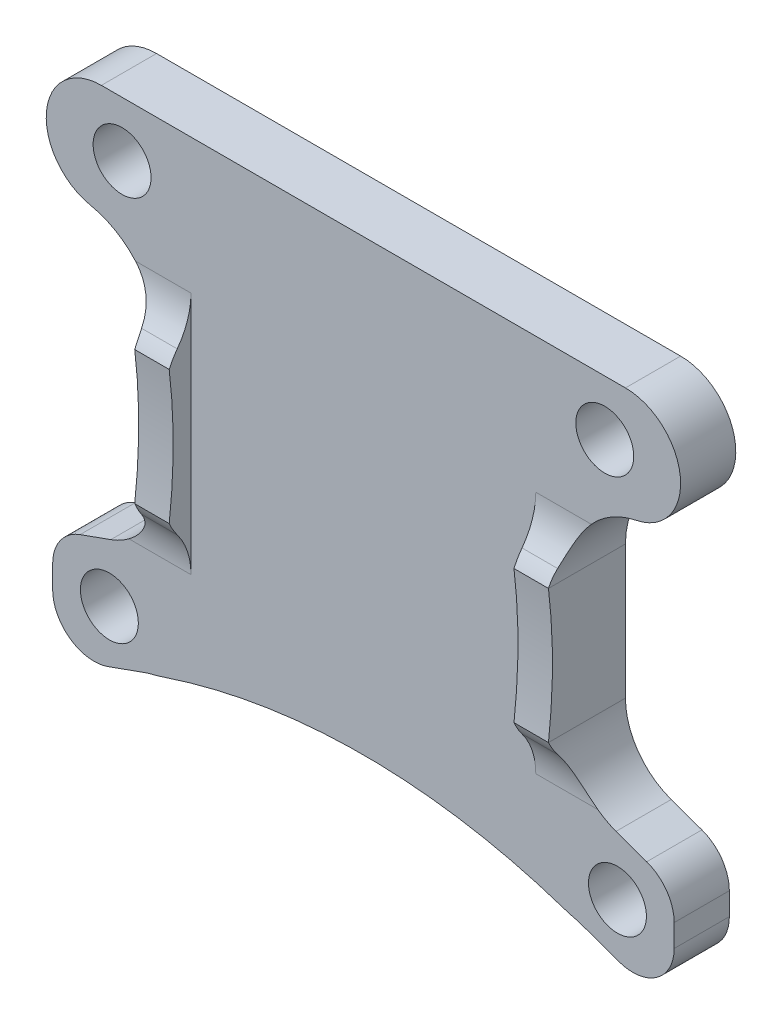
SolidWorks part; units mm, degrees
material "7075-T6 (SN)"
ref_plane "Ön Düzlem" through (0, 0, 0) normal (0, 0, 1) x (1, 0, 0)
ref_plane "Üst Düzlem" through (0, 0, 0) normal (0, 1, 0) x (1, 0, 0)
ref_plane "Sağ Düzlem" through (0, 0, 0) normal (1, 0, 0) x (0, 0, -1)
sketch "Çizim1" plane through (0, 0, 0) normal (0, 0, 1) x (1, 0, 0)
  line L1 (-14.1333, -17.5) -> (14.1333, -17.5)
  line L2 (-15, -5.9774) -> (-15, 9.5)
  line L3 (-15, 17.5) -> (15, 17.5)
  line L4 (15, -5.9774) -> (15, 9.5)
  line L5 (-15, -17.5) -> (15, 17.5) construction
  line L6 (-15, 17.5) -> (15, -17.5) construction
  line L7 (-15.8162, -17.7917) -> (-18.5235, -18.7594)
  line L8 (-18.3171, -10.6856) -> (-20.543, -11.4812)
  line L9 (-22.5333, -15.9344) -> (-22.5333, -14.3062)
  line L10 (0, -55) -> (0, 55) construction
  line L11 (15.8162, -17.7917) -> (18.5235, -18.7594)
  line L12 (22.5333, -15.9344) -> (22.5333, -14.3062)
  line L13 (18.3171, -10.6856) -> (20.543, -11.4812)
  line L14 (15, 9.5) -> (23, 9.5)
  line L15 (-15, 17.5) -> (-23, 17.5)
  line L17 (-15, 9.5) -> (-23, 9.5)
  line L18 (-23, 17.5) -> (-23, 9.5)
  line L19 (23, 17.5) -> (23, 9.5)
  line L20 (15, 17.5) -> (23, 17.5)
  arc A0 (-15, -5.9774) -> (-18.3171, -10.6856) centre (-20, -5.9774) cw
  arc A1 (-14.1333, -17.5) -> (-15.8162, -17.7917) centre (-14.1333, -22.5) ccw
  arc A2 (-18.5235, -18.7594) -> (-22.5333, -15.9344) centre (-19.5333, -15.9344) cw
  arc A3 (-20.543, -11.4812) -> (-22.5333, -14.3062) centre (-19.5333, -14.3062) ccw
  arc A4 (14.1333, -17.5) -> (15.8162, -17.7917) centre (14.1333, -22.5) cw
  arc A5 (18.5235, -18.7594) -> (22.5333, -15.9344) centre (19.5333, -15.9344) ccw
  arc A6 (15, -5.9774) -> (18.3171, -10.6856) centre (20, -5.9774) ccw
  arc A7 (20.543, -11.4812) -> (22.5333, -14.3062) centre (19.5333, -14.3062) cw
  point P0 (0, 0)
  point P11 (-15, -9.5)
  point P17 (-22.5333, -20.1926)
  point P20 (-22.5333, -12.1926)
  dimension "D5" = 5
  dimension "D6" = 5
  dimension "D7" = 3
  dimension "D1" = 30
  dimension "D2" = 35
  dimension "D3" = 8
  dimension "D4" = 8
  dimension "D8" = 8
  dimension "D9" = 8
extrude "Yükseklik-Ekstrüzyon1" add sketch "Çizim1" along normal blind 4
fillet "Radyus1" 2 edges at (23, 9.5, 2) (23, 17.5, 2) type full round first side face at (19, 9.5, 2) second side face at (0, 17.5, 2) middle face at (23, 13.5, 2)
fillet "Radyus2" 2 edges at (-23, 9.5, 2) (-23, 17.5, 2) type full round first side face at (-19, 9.5, 2) second side face at (-2, 17.5, 2) middle face at (-23, 13.5, 2)
sketch "Çizim2" plane through (0, 0, 0) normal (0, 0, -1) x (-1, 0, 0)
  circle A0 centre (0, 0) radius 9.5 construction
  point P3 (0, 9.5)
  point P7 (9.5, 0)
  point P8 (0, -9.5)
  point P9 (-9.5, 0)
  point P10 (0, 0)
  dimension "D1" = 19
sketch "Çizim5" plane through (0, 0, 0) normal (0, 0, -1) x (-1, 0, 0)
  line L0 (0, 55) -> (0, -55) construction
  circle A1 centre (-18.8837, -14.9121) radius 2 construction
  circle A2 centre (18.8837, -14.9121) radius 2 construction
  dimension "D1" = 4
fillet "Radyus3" radius 6 2 edges at (-15, 9.5, 2) (15, 9.5, 2)
sketch "Çizim8" plane through (15, 0, 0) normal (1, 0, 0) x (0, 0, -1)
  line L0 (-4, 3.702) -> (-4, -5.9774)
  line L1 (-4, 3.702) -> (-6, 3.702)
  line L2 (-4, -5.9774) -> (-6, -5.9774)
  line L3 (-6, 3.702) -> (-6, -5.9774)
  dimension "D1" = 2
extrude "Yükseklik-Ekstrüzyon2" add sketch "Çizim8" against normal blind 2.5
sketch "Çizim10" plane through (0, 0, 4) normal (0, 0, 1) x (1, 0, 0)
  line L0 (-14.9873, -17.5735) -> (14.9873, -17.5735)
  arc A0 (-14.9873, -17.5735) -> (14.9873, -17.5735) centre (0, -60.6858) cw
  arc A1 (-14.1333, -17.5) -> (-15.8162, -17.7917) centre (-14.1333, -22.5) ccw construction
  arc A2 (15.8162, -17.7917) -> (14.1333, -17.5) centre (14.1333, -22.5) ccw construction
extrude "Kes-Ekstrüzyon6" cut sketch "Çizim10" against normal through all
fillet "Radyus12" radius 10 2 edges at (14.9873, -17.5735, 2) (-14.9873, -17.5735, 2)
sketch "Çizim15" plane through (0, 0, 0) normal (0, 0, -1) x (-1, 0, 0)
  line L0 (-19, 13.5) -> (-17.5, 13.5) construction
  line L1 (0, 3.0785) -> (0, -3.0785) construction
  line L2 (19, 13.5) -> (17.5, 13.5) construction
  line L3 (-19.5333, -15.9344) -> (-18.4199, -14.9293) construction
  line L4 (19.5333, -15.9344) -> (18.4199, -14.9293) construction
  dimension "D1" = 1.5
  dimension "D2" = 1.5
hole_wizard "M4 Helisarmal için Zıvana matkabı3" positions "Çizim16" profile "Çizim17" hole size "M4x0.7" standard "ANSI Metric" end condition through all
sketch "Çizim16" plane through (0, 0, 0) normal (0, 0, -1) x (-1, 0, 0)
  point P0 (-17.5, 13.5)
  point P3 (17.5, 13.5)
  point P6 (-18.4199, -14.9293)
  point P9 (18.4199, -14.9293)
sketch "Çizim17" plane through (17.5, 13.5, 0) normal (1, 0, 0) x (0, 1, 0)
  line L0 (0, 0) -> (0, 6)
  line L1 (0, 6) -> (2.1, 6)
  line L2 (2.1, 6) -> (2.1, 0)
  line L5 (2.1, 0) -> (0, 0)
  line L11 (0, -6.35) -> (0, 107.95) construction
  dimension "Thru Hole Dia." = 4.2
  dimension "Thru Hole Depth" = 6
sketch "Çizim19" plane through (0, 0, 0) normal (0, 0, -1) x (-1, 0, 0)
  circle A0 centre (0, 0) radius 10
  dimension "D1" = 20
extrude "Kes-Ekstrüzyon9" cut sketch "Çizim19" against normal blind 1
fillet "Radyus17" radius 5 1 edges at (-10, 0, 1)
fillet "Radyus18" radius 5 2 edges at (13.75, 3.702, 4) (13.75, -5.9774, 4)
fillet "Radyus19" radius 5 2 edges at (13.75, 3.702, 6) (13.75, -5.9774, 6)
mirror "Aynalama1" about plane through (0, 0, 0) normal (1, 0, 0) of "Radyus18", "Radyus19", "Yükseklik-Ekstrüzyon2"
sketch "Çizim20" plane through (15, 0, 0) normal (1, 0, 0) x (0, 0, -1)
  line L0 (-6.1615, 1.5416) -> (-6.1615, -3.8169)
  arc A0 (-5.5826, 3.702) -> (-5.5826, -5.9774) centre (-45.9996, -1.1377) cw
  arc A1 (-5.5826, 3.702) -> (-6.1615, 1.5416) centre (-0.1781, 1.096) ccw
  arc A2 (-6.1615, -3.8169) -> (-5.5826, -5.9774) centre (-0.1781, -3.3714) ccw
  point P7 (0, 0)
extrude "Kes-Ekstrüzyon11" cut sketch "Çizim20" against normal through all and the other way through all
